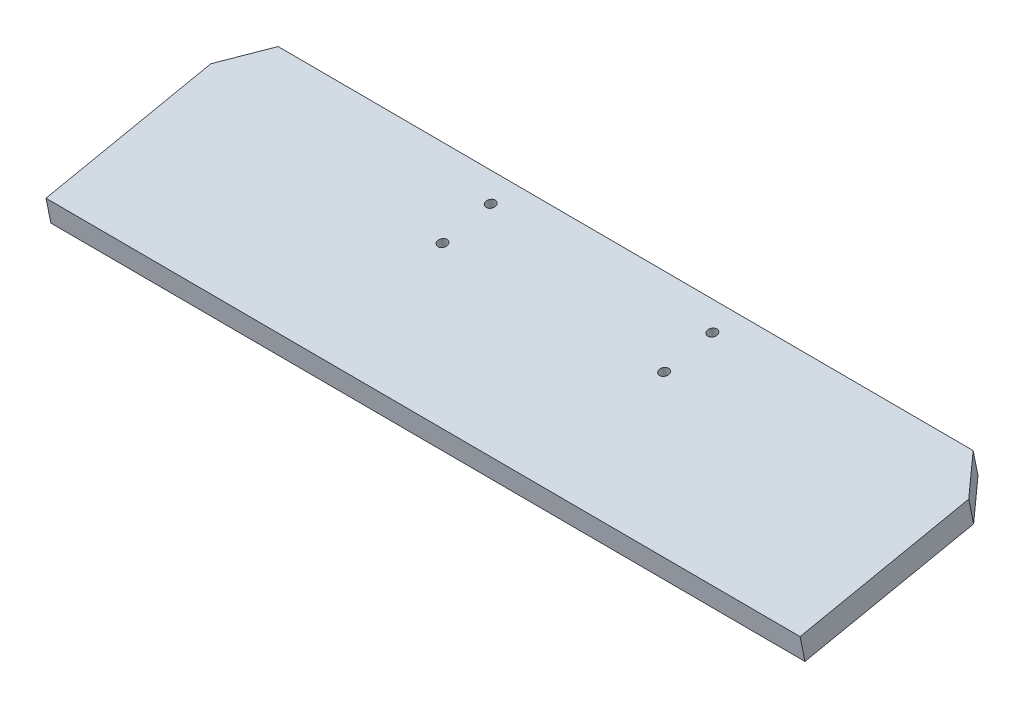
SolidWorks part; units mm, degrees
material "Plain Carbon Steel"
ref_plane "Front Plane" through (0, 0, 0) normal (0, 0, 1) x (1, 0, 0)
ref_plane "Top Plane" through (0, 0, 0) normal (0, 1, 0) x (1, 0, 0)
ref_plane "Right Plane" through (0, 0, 0) normal (1, 0, 0) x (0, 0, -1)
ref_axis "Centerline" through (0, 192.8789, -174.9002) along (0, -0.2021, 0.9794)
sketch "Sketch2" plane through (0.6833, 150.3852, 31.0298) normal (0.0045, 0.9794, 0.2021) x (-1, 0.0044, 0.0009)
  line L0 (-88.4223, 329.6639) -> (90.8089, 329.6639)
  line L1 (-96.7115, 339.2857) -> (-88.4223, 329.6639)
  line L3 (97.7546, 383.7357) -> (97.7546, 340.2962)
  line L4 (97.7546, 340.2962) -> (90.8089, 329.6639)
  line L10 (-96.7115, 383.7357) -> (-96.7115, 339.2857)
  line L11 (-96.7115, 383.7357) -> (97.7546, 383.7357)
  dimension "D1" = 12.7
extrude "Boss-Extrude1" add sketch "Sketch2" along normal blind 6.35
sketch "Sketch4" plane through (0.7116, 156.6041, 32.313) normal (0.0045, 0.9794, 0.2021) x (1, -0.0044, -0.0009)
  line L3 (-1.1933, -329.6639) -> (-1.1933, -383.7357) construction
  line L4 (88.4223, -329.6639) -> (-90.8089, -329.6639) construction
  line L5 (-97.7546, -383.7357) -> (96.7115, -383.7357) construction
  circle A0 centre (27.3817, -336.0139) radius 1.1906
  circle A1 centre (27.3817, -348.7139) radius 1.1906
  circle A2 centre (-29.7683, -348.7139) radius 1.1906
  circle A3 centre (-29.7683, -336.0139) radius 1.1906
  dimension "D1" = 2.3813
  dimension "D2" = 12.7
  dimension "D3" = 28.575
  dimension "D4" = 6.35
extrude "Cut-Extrude2" cut sketch "Sketch4" against normal through all
